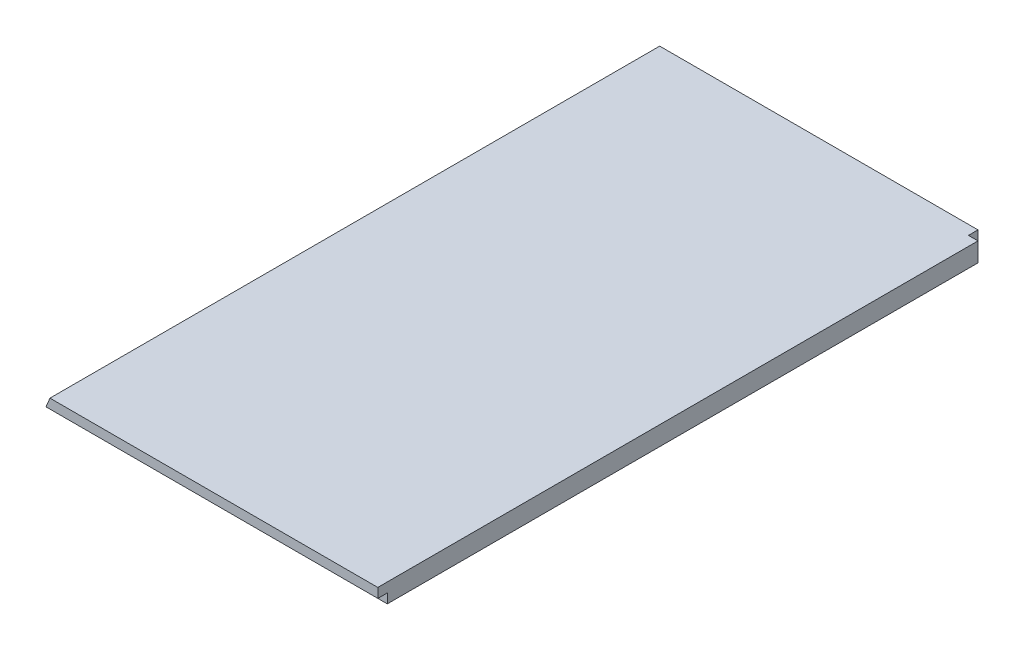
SolidWorks part; units mm, degrees
ref_plane "Front Plane" through (0, 0, 0) normal (0, 0, 1) x (1, 0, 0)
ref_plane "Top Plane" through (0, 0, 0) normal (0, 1, 0) x (1, 0, 0)
ref_plane "Right Plane" through (0, 0, 0) normal (1, 0, 0) x (0, 0, -1)
sketch "Sketch1" plane through (0, 0, 0) normal (0, 0, 1) x (1, 0, 0)
  line L0 (0, 0) -> (5.2605, 12.7)
  line L1 (5.2605, 12.7) -> (223.774, 12.7)
  line L2 (223.774, 12.7) -> (223.774, 0)
  line L3 (223.774, 0) -> (0, 0)
  dimension "D1" = 12.7
  dimension "D2" = 223.774
  dimension "D3" = 67.5
extrude "Boss-Extrude1" add sketch "Sketch1" along normal blind 406.4
sketch "Sketch2" plane through (0, 0, 0) normal (0, -1, 0) x (1, 0, 0)
  line L0 (0, 406.4) -> (0, 0) construction
  line L1 (0, 6.35) -> (223.774, 6.35)
  line L2 (0, 6.35) -> (0, 0)
  line L3 (0, 0) -> (223.774, 0)
  line L4 (223.774, 6.35) -> (223.774, 0)
  dimension "D1" = 6.35
extrude "Cut-Extrude1" cut sketch "Sketch2" against normal blind 6.35
sketch "Sketch3" plane through (0, 0, 0) normal (0, -1, 0) x (1, 0, 0)
  line L0 (223.774, 406.4) -> (223.774, 6.35) construction
  line L1 (0, 406.4) -> (223.774, 406.4)
  line L2 (0, 406.4) -> (0, 400.05)
  line L3 (0, 400.05) -> (223.774, 400.05)
  line L4 (223.774, 406.4) -> (223.774, 400.05)
  dimension "D1" = 6.35
extrude "Cut-Extrude2" cut sketch "Sketch3" against normal blind 6.35
sketch "Sketch4" plane through (0, 0, 0) normal (0, -1, 0) x (1, 0, 0)
  line L0 (223.774, 6.35) -> (0, 6.35) construction
  line L1 (223.774, 0) -> (217.424, 0)
  line L2 (223.774, 0) -> (223.774, 6.35)
  line L3 (223.774, 6.35) -> (217.424, 6.35)
  line L4 (217.424, 0) -> (217.424, 6.35)
  dimension "D1" = 6.35
extrude "Cut-Extrude3" cut sketch "Sketch4" against normal through all
